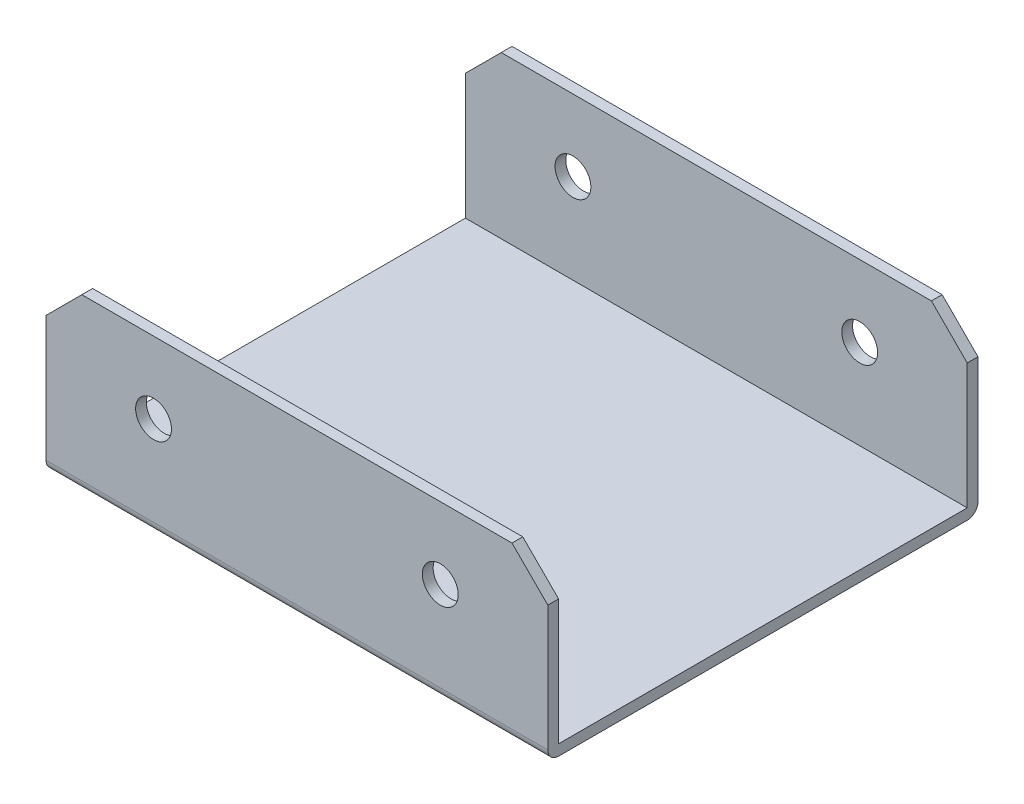
SolidWorks part; units mm, degrees
ref_plane "前基準面" through (0, 0, 0) normal (0, 0, 1) x (1, 0, 0)
ref_plane "上基準面" through (0, 0, 0) normal (0, 1, 0) x (1, 0, 0)
ref_plane "右基準面" through (0, 0, 0) normal (1, 0, 0) x (0, 0, -1)
ref_plane "平面1"
sketch "草圖1" plane through (0, 0, 0) normal (1, 0, 0) x (0, 1, 0)
  line L0 (1.5, 30) -> (1.5, 28.5)
  line L1 (1.5, 28.5) -> (24, 28.5)
  line L2 (24, 28.5) -> (24, 30)
  line L3 (24, 30) -> (1.5, 30)
  line L4 (1.5, -30) -> (24, -30)
  line L5 (24, -30) -> (24, -28.5)
  line L6 (24, -28.5) -> (1.5, -28.5)
  line L7 (1.5, -28.5) -> (1.5, -30)
  line L8 (1.5, -30) -> (1.5, 30)
  line L9 (0, 28.5) -> (0, -28.5)
  arc A0 (1.5, 30) -> (0, 28.5) centre (1.5, 28.5) ccw
  arc A1 (0, -28.5) -> (1.5, -30) centre (1.5, -28.5) ccw
  point P10 (0, 0)
extrude "擠出1" add sketch "草圖1" along normal blind 35 and the other way blind 35 contours L2 L3 L0 L1 | L6 L7 L4 L5 | L9 A1 L7 L8 L0 A0 region at (0, 12.75, 29.25) region at (0, 0.7545, 0) region at (0, 12.75, -29.25)
chamfer "倒角1" distance 5 distance2 5 4 edges at (35, 24, 29.25) (35, 24, -29.25) (-35, 24, -29.25) (-35, 24, 29.25)
sketch "草圖2" plane through (0, 0, 30) normal (0, 0, 1) x (1, 0, 0)
  circle A0 centre (-20, 14) radius 2.5
  circle A1 centre (20, 14) radius 2.5
  dimension "D2" = 5
  dimension "D3" = 5
  dimension "D1" = 40
extrude "Cut-Extrude1" cut sketch "草圖2" against normal through all
